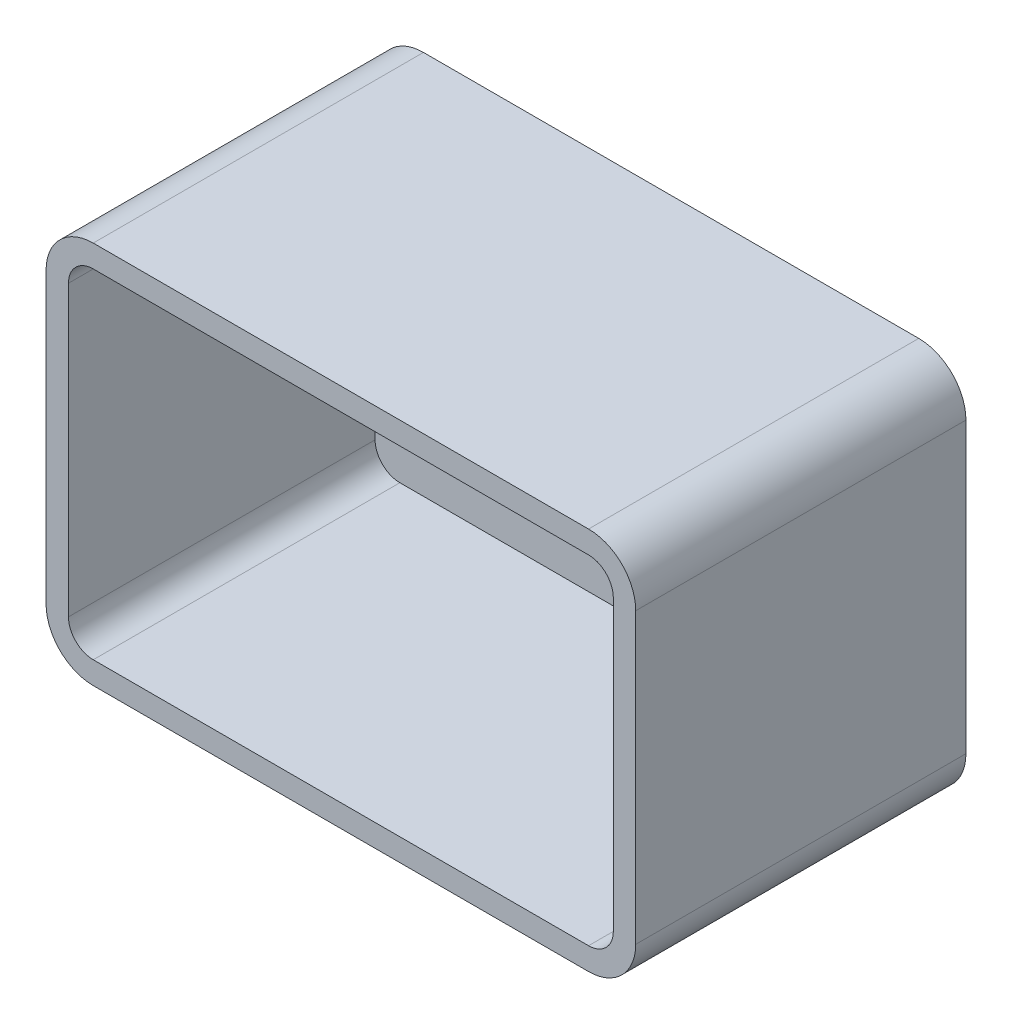
SolidWorks part; units mm, degrees
ref_plane "Front Plane" through (0, 0, 0) normal (0, 0, 1) x (1, 0, 0)
ref_plane "Top Plane" through (0, 0, 0) normal (0, 1, 0) x (1, 0, 0)
ref_plane "Right Plane" through (0, 0, 0) normal (1, 0, 0) x (0, 0, -1)
sketch "Sketch1" plane through (0, 0, 0) normal (0, 0, 1) x (1, 0, 0)
  line L0 (-21, 14.35) -> (21, 14.35)
  line L1 (-21, -16.25) -> (21, -16.25)
  line L2 (-25, -12.25) -> (-25, 12.25)
  line L3 (-21, 16.25) -> (21, 16.25)
  line L4 (25, -12.25) -> (25, 12.25)
  line L5 (-25, -16.25) -> (25, 16.25) construction
  line L6 (-25, 16.25) -> (25, -16.25) construction
  line L7 (23.1, -12.25) -> (23.1, 12.25)
  line L8 (-21, -14.35) -> (21, -14.35)
  line L9 (-23.1, -12.25) -> (-23.1, 12.25)
  line L14 (0, 0) -> (-29.0236, 0) construction
  line L16 (-19.5, -9) -> (-14.5, -9)
  line L17 (-20.5, -8) -> (-20.5, 8)
  line L18 (-19.5, 9) -> (-14.5, 9)
  line L19 (-13.5, -8) -> (-13.5, 8)
  line L20 (-20.5, -9) -> (-13.5, 9) construction
  line L21 (-20.5, 9) -> (-13.5, -9) construction
  arc A0 (21, 16.25) -> (25, 12.25) centre (21, 12.25) cw
  arc A1 (21, -16.25) -> (25, -12.25) centre (21, -12.25) ccw
  arc A2 (-21, -16.25) -> (-25, -12.25) centre (-21, -12.25) cw
  arc A3 (-25, 12.25) -> (-21, 16.25) centre (-21, 12.25) cw
  arc A4 (21, 14.35) -> (23.1, 12.25) centre (21, 12.25) cw
  arc A5 (21, -14.35) -> (23.1, -12.25) centre (21, -12.25) ccw
  arc A6 (-21, -14.35) -> (-23.1, -12.25) centre (-21, -12.25) cw
  arc A7 (-23.1, 12.25) -> (-21, 14.35) centre (-21, 12.25) cw
  arc A14 (-19.5, -9) -> (-20.5, -8) centre (-19.5, -8) cw
  arc A15 (-14.5, -9) -> (-13.5, -8) centre (-14.5, -8) ccw
  arc A16 (-14.5, 9) -> (-13.5, 8) centre (-14.5, 8) cw
  arc A17 (-20.5, 8) -> (-19.5, 9) centre (-19.5, 8) cw
  point P0 (0, 0)
  point P32 (-17, 0)
  point P49 (-17, -9)
  point P50 (25, 0)
  dimension "D2" = 4
  dimension "D6" = 17
  dimension "D7" = 18
  dimension "D5" = 1
  dimension "D1" = 50
  dimension "D3" = 32.5
  dimension "D8" = 7
  dimension "D4" = 1.9
extrude "Boss-Extrude1" add sketch "Sketch1" along normal blind 28 contours A3 L2 A2 L1 A1 L4 A0 L3 L9 A7 L0 A4 L7 A5 L8 A6 region at (-23.4067, -14.6567, 0)
extrude "Boss-Extrude2" add sketch "Sketch1<3>" along normal blind 2 contours A7 L9 A6 L8 A5 L7 A4 L0 L17 A17 L18 A16 L19 A15 L16 A14 region at (1.7773, 0, 0)
sketch "Sketch1<3>" plane through (0, 0, 0) normal (0, 0, 1) x (1, 0, 0) same geometry as "Sketch1"
